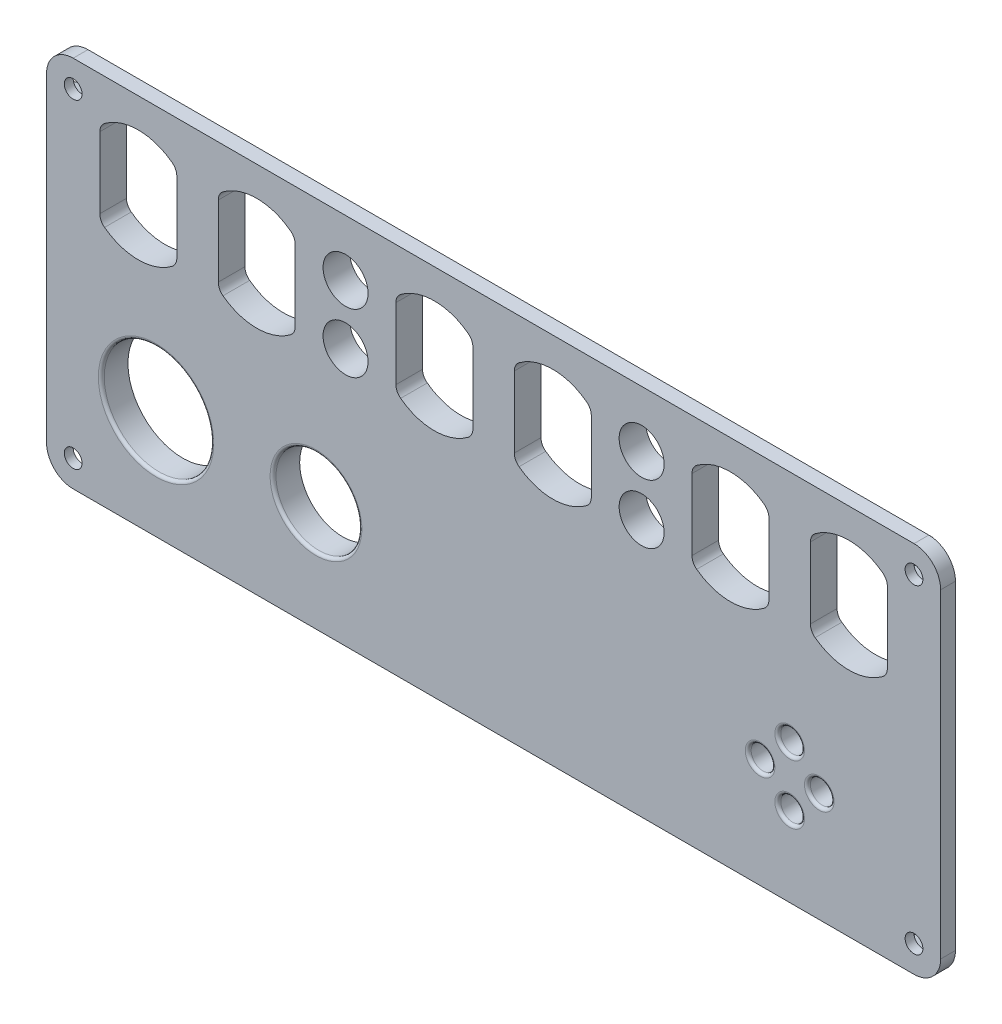
SolidWorks part; units mm, degrees
ref_plane "前视基准面" through (0, 0, 0) normal (0, 0, 1) x (1, 0, 0)
ref_plane "上视基准面" through (0, 0, 0) normal (0, 1, 0) x (1, 0, 0)
ref_plane "右视基准面" through (0, 0, 0) normal (1, 0, 0) x (0, 0, -1)
sketch "草图1" plane through (0, 0, 0) normal (0, 0, 1) x (1, 0, 0)
  line L0 (0, -31.5) -> (0, 31.5) construction
  line L1 (-71, 31.5) -> (71, 31.5)
  line L2 (-75.5, 27) -> (-75.5, -27)
  line L3 (-71, -31.5) -> (71, -31.5)
  line L4 (75.5, 27) -> (75.5, -27)
  line L5 (-75.5, 31.5) -> (75.5, -31.5) construction
  line L6 (-75.5, -31.5) -> (75.5, 31.5) construction
  line L7 (-75.5, 0) -> (75.5, 0) construction
  arc A0 (-71, -31.5) -> (-75.5, -27) centre (-71, -27) cw
  arc A1 (71, -31.5) -> (75.5, -27) centre (71, -27) ccw
  arc A2 (75.5, 27) -> (71, 31.5) centre (71, 27) ccw
  arc A3 (-71, 31.5) -> (-75.5, 27) centre (-71, 27) ccw
  circle A4 centre (-71, 27) radius 1.5
  circle A5 centre (71, 27) radius 1.5
  circle A6 centre (71, -27) radius 1.5
  circle A7 centre (-71, -27) radius 1.5
  point P0 (0, 0)
  dimension "D3" = 4.5
  dimension "D4" = 3
  dimension "D1" = 151
  dimension "D2" = 63
extrude "凸台-拉伸1" add sketch "草图1" against normal blind 4.5
sketch "草图2" plane through (0, 0, -4.5) normal (0, 0, -1) x (-1, 0, 0)
  line L1 (-71, 23.7) -> (-68.1421, 25.35)
  line L2 (-68.1421, 25.35) -> (-68.1421, 28.65)
  line L3 (-68.1421, 28.65) -> (-71, 30.3)
  line L4 (-71, 30.3) -> (-73.8579, 28.65)
  line L5 (-73.8579, 28.65) -> (-73.8579, 25.35)
  line L6 (-73.8579, 25.35) -> (-71, 23.7)
  line L7 (0, 0) -> (0, 31.5) construction
  line L8 (-71, 31.5) -> (71, 31.5) construction
  line L9 (0, 0) -> (-75.5, 0) construction
  line L10 (-75.5, -27) -> (-75.5, 27) construction
  line L11 (71, 30.3) -> (73.8579, 28.65)
  line L12 (73.8579, 28.65) -> (73.8579, 25.35)
  line L13 (73.8579, 25.35) -> (71, 23.7)
  line L14 (71, 23.7) -> (68.1421, 25.35)
  line L15 (68.1421, 25.35) -> (68.1421, 28.65)
  line L16 (68.1421, 28.65) -> (71, 30.3)
  line L17 (73.8579, -28.65) -> (73.8579, -25.35)
  line L18 (71, -30.3) -> (73.8579, -28.65)
  line L19 (68.1421, -28.65) -> (71, -30.3)
  line L20 (68.1421, -25.35) -> (68.1421, -28.65)
  line L21 (71, -23.7) -> (68.1421, -25.35)
  line L22 (73.8579, -25.35) -> (71, -23.7)
  line L23 (-71, -30.3) -> (-73.8579, -28.65)
  line L24 (-73.8579, -28.65) -> (-73.8579, -25.35)
  line L25 (-73.8579, -25.35) -> (-71, -23.7)
  line L26 (-71, -23.7) -> (-68.1421, -25.35)
  line L27 (-68.1421, -25.35) -> (-68.1421, -28.65)
  line L28 (-68.1421, -28.65) -> (-71, -30.3)
  circle A0 centre (-71, 27) radius 1.5 construction
  circle A1 centre (-71, 27) radius 1.5
  circle A2 centre (-71, 27) radius 3.3 construction
  circle A3 centre (-71, 27) radius 2.8579 construction
  dimension "D1" = 6.6
  dimension "D2" = 2.8579
extrude "切除-拉伸1" cut sketch "草图2" against normal blind 3
sketch "草图3" plane through (0, 0, 0) normal (0, 0, 1) x (1, 0, 0)
  line L0 (0, 0) -> (0, 31.5) construction
  line L1 (71, 31.5) -> (-71, 31.5) construction
  line L2 (-66.5, 17) -> (66.9091, 17) construction
  line L5 (-53.5, 17) -> (-53.5, 23.9282)
  line L6 (-53.5, 17) -> (-53.5, 10.0718)
  line L8 (-60, 17) -> (-60, 31.5) construction
  line L10 (-50, 17) -> (-50, 31.5) construction
  line L13 (-35, 17) -> (-35, 31.5) construction
  line L22 (66.9091, 22) -> (-50, 22) construction
  line L23 (-66.5, 17) -> (-66.5, 10.0718)
  line L24 (-66.5, 17) -> (-66.5, 23.9282)
  line L25 (-33.5, 17) -> (-33.5, 10.0718)
  line L26 (-33.5, 17) -> (-33.5, 23.9282)
  line L27 (-46.5, 17) -> (-46.5, 23.9282)
  line L28 (-46.5, 17) -> (-46.5, 10.0718)
  line L29 (-25, 22) -> (-25, 12) construction
  line L30 (-3.5, 17) -> (-3.5, 10.0718)
  line L31 (-16.5, 17) -> (-16.5, 10.0718)
  line L32 (-16.5, 17) -> (-16.5, 23.9282)
  line L33 (-3.5, 17) -> (-3.5, 23.9282)
  line L34 (16.5, 17) -> (16.5, 10.0718)
  line L35 (3.5, 17) -> (3.5, 10.0718)
  line L36 (3.5, 17) -> (3.5, 23.9282)
  line L37 (16.5, 17) -> (16.5, 23.9282)
  line L38 (46.5, 17) -> (46.5, 10.0718)
  line L39 (33.5, 17) -> (33.5, 10.0718)
  line L40 (33.5, 17) -> (33.5, 23.9282)
  line L41 (46.5, 17) -> (46.5, 23.9282)
  line L42 (53.5, 17) -> (53.5, 10.0718)
  line L43 (53.5, 17) -> (53.5, 23.9282)
  line L44 (66.5, 17) -> (66.5, 23.9282)
  line L45 (66.5, 17) -> (66.5, 10.0718)
  circle A12 centre (-25, 22) radius 3.8
  circle A13 centre (-25, 12) radius 3.8
  circle A14 centre (25, 12) radius 3.8
  circle A15 centre (25, 22) radius 3.8
  arc A16 (-53.5, 23.9282) -> (-66.5, 23.9282) centre (-60, 17) ccw
  arc A17 (-66.5, 10.0718) -> (-53.5, 10.0718) centre (-60, 17) ccw
  arc A18 (-33.5, 10.0718) -> (-46.5, 10.0718) centre (-40, 17) cw
  arc A19 (-46.5, 23.9282) -> (-33.5, 23.9282) centre (-40, 17) cw
  arc A20 (-16.5, 10.0718) -> (-3.5, 10.0718) centre (-10, 17) ccw
  arc A21 (-3.5, 23.9282) -> (-16.5, 23.9282) centre (-10, 17) ccw
  arc A22 (16.5, 10.0718) -> (3.5, 10.0718) centre (10, 17) cw
  arc A23 (3.5, 23.9282) -> (16.5, 23.9282) centre (10, 17) cw
  arc A24 (33.5, 10.0718) -> (46.5, 10.0718) centre (40, 17) ccw
  arc A25 (46.5, 23.9282) -> (33.5, 23.9282) centre (40, 17) ccw
  arc A26 (66.5, 10.0718) -> (53.5, 10.0718) centre (60, 17) cw
  arc A27 (53.5, 23.9282) -> (66.5, 23.9282) centre (60, 17) cw
  point P5 (0, 17)
  point P6 (-60, 17)
  point P13 (-50, 17)
  point P14 (-35, 17)
  point P15 (-66.5, 17)
  point P18 (-53.5, 17)
  point P52 (0, 22)
  point P53 (-25, 22)
  dimension "D5" = 19
  dimension "D10" = 7.6
  dimension "D1" = 17
  dimension "D2" = 60
  dimension "D3" = 50
  dimension "D4" = 35
  dimension "D6" = 6.5
  dimension "D7" = 6.5
  dimension "D8" = 5
  dimension "D9" = 25
extrude "切除-拉伸2" cut sketch "草图3" against normal blind 6
sketch "草图4" plane through (0, 0, 0) normal (0, 0, 1) x (1, 0, 0)
  line L0 (0, 0) -> (-75.5, 0) construction
  line L1 (-75.5, 27) -> (-75.5, -27) construction
  line L2 (-57, 0) -> (-57, -31.5) construction
  line L3 (-71, -31.5) -> (71, -31.5) construction
  line L4 (-30, 0) -> (-30, -31.5) construction
  line L5 (-30, -13) -> (-66.25, -13) construction
  circle A0 centre (-57, -13) radius 9.25
  circle A1 centre (-30, -13) radius 7.25
  point P5 (-57, 0)
  point P6 (-30, 0)
  point P13 (-57, -13)
  point P19 (-30, -13)
  dimension "D4" = 18.5
  dimension "D5" = 14.5
  dimension "D1" = 57
  dimension "D2" = 30
  dimension "D3" = 13
extrude "切除-拉伸3" cut sketch "草图4" against normal blind 6
sketch "草图5" plane through (0, 0, -4.5) normal (0, 0, -1) x (-1, 0, 0)
  line L0 (30, -13) -> (-79.0805, -13) construction
  line L1 (0, 0) -> (0, -13) construction
  line L2 (-50, -13) -> (-41.5664, -4.5664) construction
  circle A0 centre (30, -13) radius 7.25 construction
  circle A1 centre (30, -13) radius 7.25 construction
  circle A2 centre (-45, -13) radius 2
  circle A3 centre (-55, -13) radius 2
  circle A4 centre (-50, -8) radius 2
  circle A5 centre (-50, -18) radius 2
  point P7 (-50, -13)
  point P8 (-45, -13)
  point P10 (-55, -13)
  dimension "D4" = 4
  dimension "D5" = 4
  dimension "D1" = 50
  dimension "D2" = 5
  dimension "D3" = 5
extrude "切除-拉伸4" cut sketch "草图5" against normal blind 5
fillet "圆角1" radius 2 24 edges at (-53.5, 23.9282, -2.25) (-53.5, 10.0718, -2.25) (-66.5, 10.0718, -2.25) (-66.5, 23.9282, -2.25) (-46.5, 23.9282, -2.25) (-46.5, 10.0718, -2.25) (-33.5, 10.0718, -2.25) (-33.5, 23.9282, -2.25) (-3.5, 10.0718, -2.25) (-3.5, 23.9282, -2.25) (-16.5, 10.0718, -2.25) (-16.5, 23.9282, -2.25) (3.5, 23.9282, -2.25) (16.5, 23.9282, -2.25) (16.5, 10.0718, -2.25) (3.5, 10.0718, -2.25) (33.5, 10.0718, -2.25) (46.5, 23.9282, -2.25) (46.5, 10.0718, -2.25) (33.5, 23.9282, -2.25) (53.5, 23.9282, -2.25) (53.5, 10.0718, -2.25) (66.5, 23.9282, -2.25) (66.5, 10.0718, -2.25)
sketch "草图6" plane through (0, 0, -4.5) normal (0, 0, -1) x (-1, 0, 0)
  line L0 (-75.5, -27) -> (-75.5, 27) construction
  line L1 (71, -29.5) -> (-71, -29.5)
  line L2 (73.5, -27) -> (73.5, 27)
  line L3 (71, 29.5) -> (-71, 29.5)
  line L4 (-73.5, -27) -> (-73.5, 27)
  line L5 (73.5, -29.5) -> (-73.5, 29.5) construction
  line L6 (73.5, 29.5) -> (-73.5, -29.5) construction
  line L7 (-75.5, -27) -> (-75.5, 27)
  line L8 (-71, 31.5) -> (71, 31.5) construction
  line L9 (-71, 31.5) -> (71, 31.5)
  line L10 (75.5, 27) -> (75.5, -27) construction
  line L11 (75.5, 27) -> (75.5, -27)
  line L12 (71, -31.5) -> (-71, -31.5) construction
  line L13 (71, -31.5) -> (-71, -31.5)
  line L14 (-73.8579, -28.65) -> (-71, -30.3) construction
  line L15 (-73.8579, -28.65) -> (-71, -30.3) construction
  line L16 (-73.8579, -25.35) -> (-73.8579, -28.65) construction
  line L17 (-73.8579, -25.35) -> (-73.8579, -28.65) construction
  line L18 (-71, -30.3) -> (-68.1421, -28.65) construction
  line L19 (-71, -30.3) -> (-68.1421, -28.65) construction
  circle A0 centre (-71, 27) radius 1.5 construction
  circle A1 centre (-71, 27) radius 1.5 construction
  arc A2 (73.5, 27) -> (71, 29.5) centre (71, 27) ccw
  arc A3 (71, -29.5) -> (73.5, -27) centre (71, -27) ccw
  arc A4 (-71, -29.5) -> (-73.5, -27) centre (-71, -27) cw
  arc A5 (-71, 29.5) -> (-73.5, 27) centre (-71, 27) ccw
  arc A6 (-71, 31.5) -> (-75.5, 27) centre (-71, 27) ccw construction
  arc A7 (-71, 31.5) -> (-75.5, 27) centre (-71, 27) ccw
  arc A8 (75.5, 27) -> (71, 31.5) centre (71, 27) ccw construction
  arc A9 (75.5, 27) -> (71, 31.5) centre (71, 27) ccw
  arc A10 (71, -31.5) -> (75.5, -27) centre (71, -27) ccw construction
  arc A11 (71, -31.5) -> (75.5, -27) centre (71, -27) ccw
  arc A12 (-75.5, -27) -> (-71, -31.5) centre (-71, -27) ccw construction
  arc A13 (-75.5, -27) -> (-71, -31.5) centre (-71, -27) ccw
  point P0 (0, 0)
  dimension "D4" = 2.5
  dimension "D1" = 147
  dimension "D2" = 59
  dimension "D3" = 2.5
  dimension "D5" = 2
  dimension "D6" = 1.2
  dimension "D7" = 1.6421
extrude "切除-拉伸5" cut sketch "草图6" against normal blind 2
fillet "圆角2" radius 1 4 edges at (0, -29.5, -2.5) (73.5, 0, -2.5) (0, 29.5, -2.5) (-73.5, 0, -2.5)
fillet "圆角3" radius 0.5 4 edges at (53, -13, 0) (48, -18, 0) (43, -13, 0) (48, -8, 0)
fillet "圆角4" radius 0.5 2 edges at (-47.75, -13, 0) (-22.75, -13, 0)
